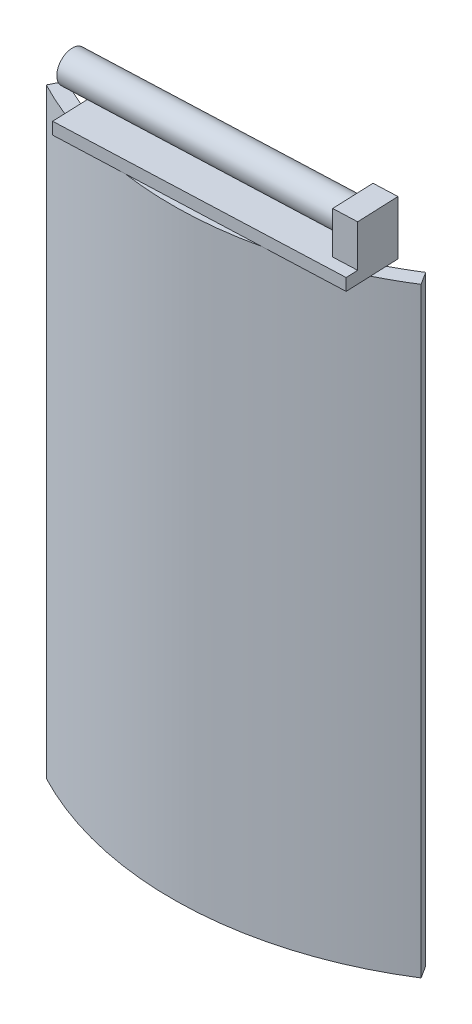
SolidWorks part; units mm, degrees
ref_plane "Front Plane" through (0, 0, 0) normal (0, 0, 1) x (1, 0, 0)
ref_plane "Top Plane" through (0, 0, 0) normal (0, 1, 0) x (1, 0, 0)
ref_plane "Right Plane" through (0, 0, 0) normal (1, 0, 0) x (0, 0, -1)
sketch "Sketch1" plane through (0, 0, 0) normal (0, 1, 0) x (1, 0, 0)
  line L3 (-33.9264, -64.6657) -> (-35.3858, -67.4854)
  line L4 (39.0385, -61.7142) -> (40.7508, -64.388)
  circle A0 centre (0, 0) radius 76.2 construction
  arc A1 (-35.3858, -67.4854) -> (40.7508, -64.388) centre (0, 0) ccw
  circle A2 centre (0, 0) radius 73.025 construction
  arc A3 (39.0385, -61.7142) -> (-33.9264, -64.6657) centre (0, 0) cw
extrude "Boss-Extrude1" add sketch "Sketch1" along normal blind 127
ref_plane "Plane1" through (2.556, 0, 63.1899) normal (0.0404, 0, 0.9992) x (0.9992, 0, -0.0404)
sketch "Sketch4" plane through (2.556, 0, 63.1899) normal (0.0404, 0, 0.9992) x (0.9992, 0, -0.0404)
  line L0 (36.5123, 127) -> (-36.5123, 127) construction
  line L1 (-36.5123, 127) -> (-36.5123, 0) construction
  line L2 (0, 127) -> (6.35, 127) construction
  line L3 (0, 127) -> (-6.35, 127) construction
  line L4 (0, 127) -> (0, 0) construction
  line L5 (0, 0) -> (-6.35, 0) construction
  line L6 (6.35, 127) -> (-6.35, 127)
  line L7 (6.35, 127) -> (6.35, 0)
  line L8 (-6.35, 127) -> (-6.35, 0)
  line L9 (6.35, 0) -> (-6.35, 0)
extrude "Boss-Extrude3" add sketch "Sketch4" along normal up to surface (9.5068 mm away) up to face at (2.7537, 63.5, 68.0776)
sketch "Sketch15" plane through (2.556, 0, 63.1899) normal (-0.0404, 0, -0.9992) x (-0.9992, 0, 0.0404)
  line L4 (-6.35, 127) -> (6.35, 127)
  line L5 (-6.35, 127) -> (-6.35, 0.0039)
  line L6 (6.35, 127) -> (6.35, 0.0039)
  line L7 (-6.35, 0.0039) -> (6.35, 0.0039)
extrude "Boss-Extrude13" add sketch "Sketch15" along normal blind 1.016
sketch "Sketch20" plane through (2.515, 0, 62.1748) normal (-0.0404, 0, -0.9992) x (-0.9992, 0, 0.0404)
  line L0 (-6.35, 0.0039) -> (-6.35, 82.5804) construction
  line L1 (-6.35, 0) -> (-6.35, 127) construction
  line L7 (-6.35, 82.5804) -> (6.35, 82.5804)
  line L8 (-6.35, 82.5804) -> (-6.35, 73.6904)
  line L9 (6.35, 82.5804) -> (6.35, 73.6904)
  line L10 (-6.35, 73.6904) -> (6.35, 73.6904)
  line L11 (6.35, 127) -> (6.35, 0) construction
extrude "Boss-Extrude18" add sketch "Sketch20" along normal blind 15.24
sketch "Sketch22" plane through (-6.3448, 0, 0.2566) normal (-0.9992, 0, 0.0404) x (0.0404, 0, 0.9992)
  line L0 (46.9856, 73.6904) -> (52.0656, 73.6904) construction
  line L1 (46.9856, 73.6904) -> (62.2256, 73.6904) construction
  circle A2 centre (52.0656, 78.1354) radius 3.302
extrude "Cut-Extrude5" cut sketch "Sketch22" against normal blind 13.97
sketch "Sketch23" plane through (0, 127, 0) normal (0, 1, 0) x (1, 0, 0)
  line L0 (28.8673, -75.173) -> (-22.6723, -77.101) construction
  line L5 (-25.5234, -76.0193) -> (34.1178, -73.6068)
  line L8 (-25.5234, -76.0193) -> (-25.9854, -64.5986)
  line L9 (-3.8298, -62.4314) -> (8.8598, -61.9181) construction
  line L14 (-25.5234, -76.0193) -> (34.1178, -73.6068) construction
  line L15 (34.1178, -73.6068) -> (33.6559, -62.1862)
  line L16 (-25.9854, -64.5986) -> (33.6559, -62.1862)
  arc A1 (-35.3858, -67.4854) -> (40.7508, -64.388) centre (0, 0) ccw construction
  point P3 (3.0975, -76.137)
  point P9 (2.515, -62.1748)
extrude "Boss-Extrude23" add sketch "Sketch23" along normal blind 2.54
sketch "Sketch29" plane through (0, 129.54, 0) normal (0, 1, 0) x (1, 0, 0)
  line L18 (33.6559, -62.1862) -> (34.0152, -71.0689)
  line L19 (33.6559, -62.1862) -> (28.58, -62.3915)
  line L20 (34.0152, -71.0689) -> (28.9393, -71.2742)
  line L21 (28.58, -62.3915) -> (28.9393, -71.2742)
  line L22 (34.1178, -73.6068) -> (33.6559, -62.1862) construction
extrude "Boss-Extrude24" add sketch "Sketch29" along normal blind 8.89
sketch "Sketch30" plane through (26.0137, 0, -1.0523) normal (-0.9992, 0, 0.0404) x (0.0404, 0, 0.9992)
  line L0 (67.9406, 138.43) -> (67.9406, 134.747) construction
  line L1 (63.4956, 138.43) -> (72.3856, 138.43) construction
  circle A0 centre (67.9406, 134.747) radius 3.302
extrude "Boss-Extrude25" add sketch "Sketch30" along normal blind 57.15
